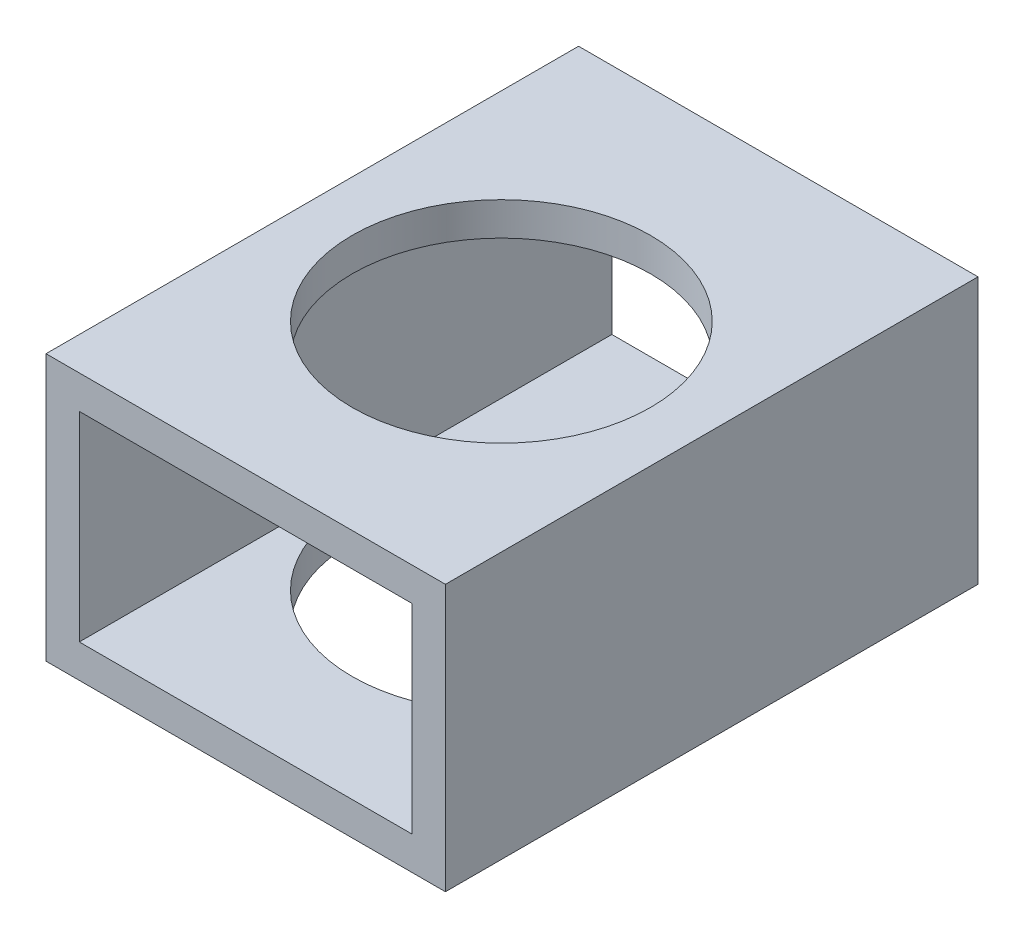
SolidWorks part; units mm, degrees
ref_plane "Front" through (0, 0, 0) normal (0, 0, 1) x (1, 0, 0)
ref_plane "Top" through (0, 0, 0) normal (0, 1, 0) x (1, 0, 0)
ref_plane "Right" through (0, 0, 0) normal (1, 0, 0) x (0, 0, -1)
sketch "Sketch1" plane through (0, 0, 0) normal (0, 0, 1) x (1, 0, 0)
  line L1 (-44.8643, 21.1125) -> (-6.7643, 21.1125)
  line L2 (-44.8643, 21.1125) -> (-44.8643, -4.2875)
  line L3 (-44.8643, -4.2875) -> (-6.7643, -4.2875)
  line L4 (-6.7643, 21.1125) -> (-6.7643, -4.2875)
  dimension "D1" = 38.1
  dimension "D2" = 25.4
extrude "Boss-Extrude1" add sketch "Sketch1" along normal blind 50.8
sketch "Sketch2" plane through (0, 0, 0) normal (0, 0, -1) x (-1, 0, 0)
  line L8 (41.6893, -1.1125) -> (41.6893, 17.9375)
  line L9 (41.6893, 17.9375) -> (9.9393, 17.9375)
  line L10 (9.9393, 17.9375) -> (9.9393, -1.1125)
  line L11 (9.9393, -1.1125) -> (41.6893, -1.1125)
  line L12 (41.6893, -1.1125) -> (41.6893, 17.9375)
  line L13 (41.6893, 17.9375) -> (9.9393, 17.9375)
  line L14 (9.9393, 17.9375) -> (9.9393, -1.1125)
  line L15 (9.9393, -1.1125) -> (41.6893, -1.1125)
  dimension "D1" = 3.175
extrude "Cut-Extrude1" cut sketch "Sketch2" against normal through all
sketch "Sketch3" plane through (0, 21.1125, 0) normal (0, 1, 0) x (1, 0, 0)
  line L0 (-25.8143, 0) -> (-25.8143, -26.416)
  line L4 (-6.7643, 0) -> (-44.8643, 0) construction
  circle A0 centre (-25.8143, -26.416) radius 14.224
extrude "Cut-Extrude3" cut sketch "Sketch3" against normal through all contours A0 region at (-35.5877, 21.1125, 36.1894)
